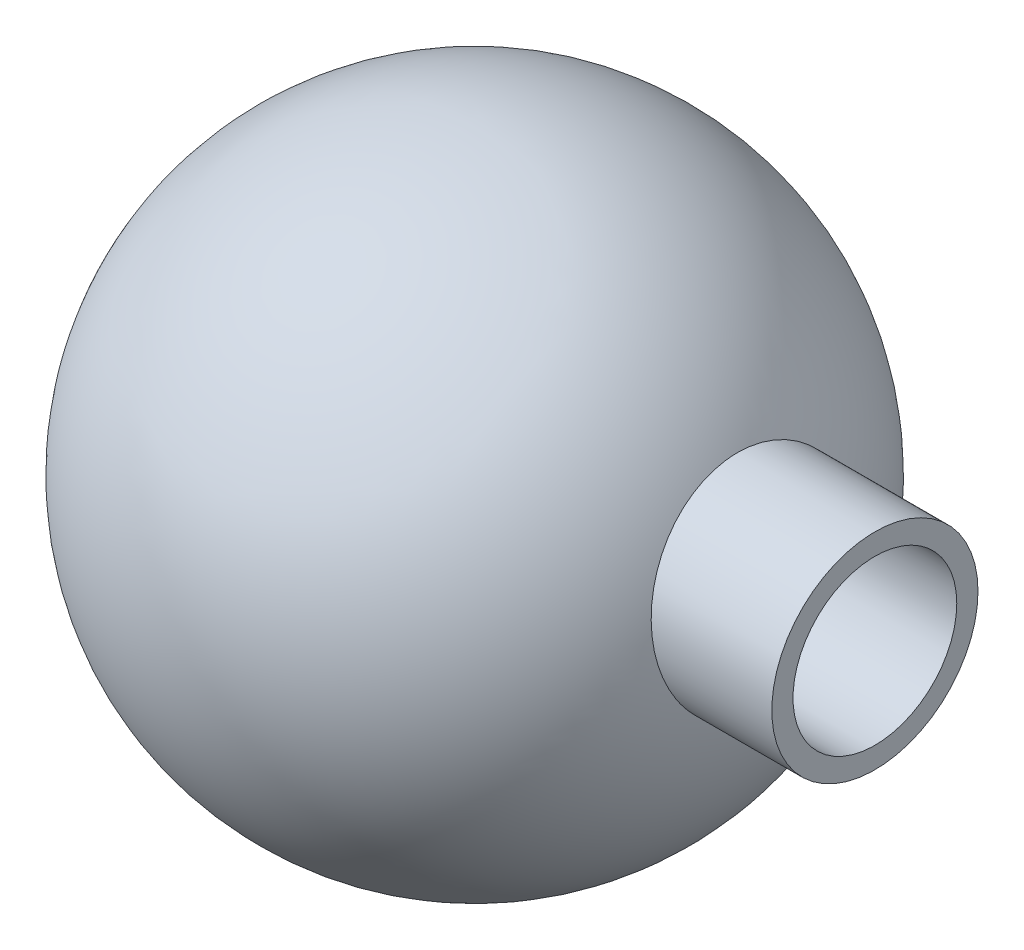
SolidWorks part; units mm, degrees
ref_plane "Front Plane" through (0, 0, 0) normal (0, 0, 1) x (1, 0, 0)
ref_plane "Top Plane" through (0, 0, 0) normal (0, 1, 0) x (1, 0, 0)
ref_plane "Right Plane" through (0, 0, 0) normal (1, 0, 0) x (0, 0, -1)
sketch "Sketch1" plane through (0, 0, 0) normal (0, 0, 1) x (1, 0, 0)
  line L0 (-63.5, 0) -> (-60.96, 0)
  line L1 (60.96, 0) -> (63.5, 0)
  arc A0 (63.5, 0) -> (-63.5, 0) centre (0, 0) ccw
  arc A1 (60.96, 0) -> (-60.96, 0) centre (0, 0) ccw
  dimension "D1" = 63.5
  dimension "D2" = 60.96
revolve "Revolve1" add sketch "Sketch1" angle 360 about L0
sketch "Sketch2" plane through (0, 0, 0) normal (1, 0, 0) x (0, 0, -1)
  line L0 (0, 69.85) -> (0, -69.85) construction
  line L1 (69.85, 0) -> (-69.85, 0) construction
  circle A0 centre (0, 10.0076) radius 21.59
  circle A1 centre (0, 10.0076) radius 17.145
  dimension "D1" = 10.0076
  dimension "D2" = 34.29
  dimension "D3" = 43.18
extrude "Boss-Extrude1" add sketch "Sketch2" along normal blind 83.82 and the other way up to next
extrude "Cut-Extrude3" cut sketch "Sketch2<4>" along normal blind 138.938 contours A1
sketch "Sketch2<4>" plane through (0, 0, 0) normal (1, 0, 0) x (0, 0, -1) same geometry as "Sketch2"
